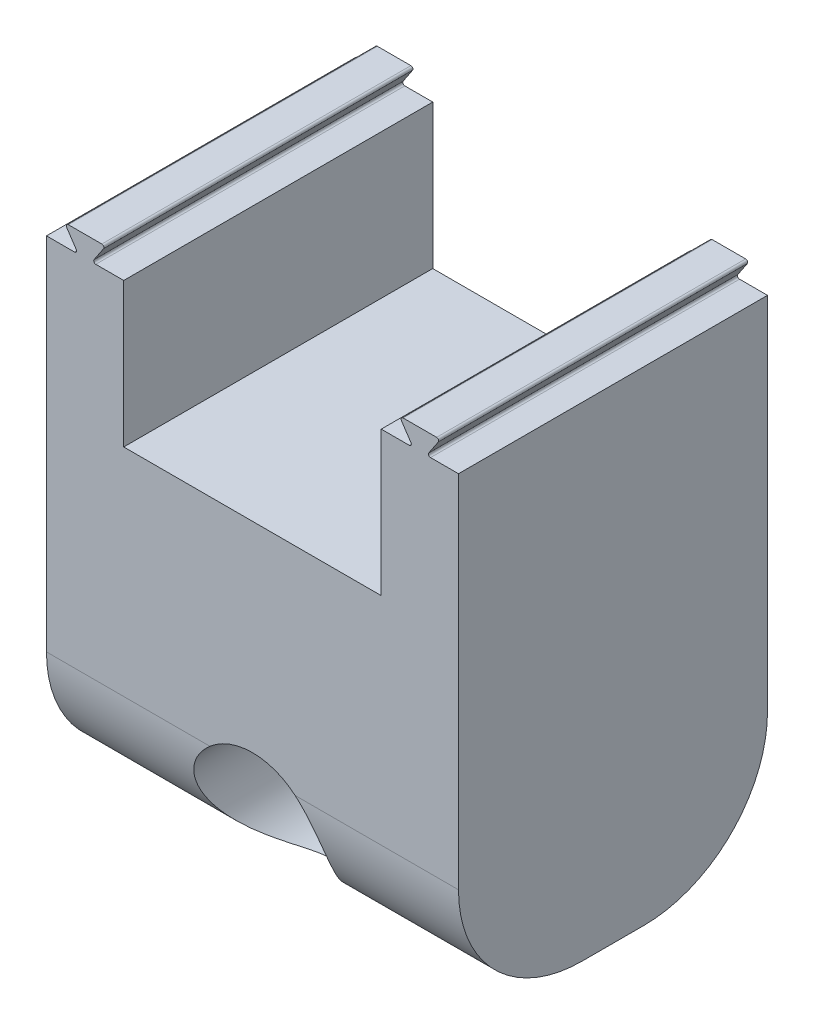
SolidWorks part; units mm, degrees
ref_plane "Front Plane" through (0, 0, 0) normal (0, 0, 1) x (1, 0, 0)
ref_plane "Top Plane" through (0, 0, 0) normal (0, 1, 0) x (1, 0, 0)
ref_plane "Right Plane" through (0, 0, 0) normal (1, 0, 0) x (0, 0, -1)
sketch "Sketch1" plane through (0, 0, 0) normal (0, 0, 1) x (1, 0, 0)
  line L2 (55, -10) -> (55, 10)
  line L3 (55, 10) -> (-55, 10)
  line L4 (-55, -10) -> (-55, 10)
  line L5 (55, -10) -> (-55, 10) construction
  line L6 (55, 10) -> (-55, -10) construction
  line L18 (40, -84.8211) -> (60, -84.8211)
  line L19 (55, -37.8397) -> (60, -37.8397)
  line L20 (55, -37.8397) -> (45, -37.8397) construction
  line L21 (43.75, -54.3304) -> (56.25, -54.3304)
  line L22 (43.75, -54.3304) -> (43.75, -68.3304)
  line L23 (43.75, -68.3304) -> (56.25, -68.3304)
  line L24 (56.25, -54.3304) -> (56.25, -68.3304)
  line L25 (50, -41.4304) -> (50, -81.2304) construction
  line L28 (40, -37.8397) -> (45, -37.8397)
  line L29 (-55, -10) -> (45, -10)
  line L30 (55, -10) -> (55, -37.8397)
  line L31 (45, -37.8397) -> (45, -10)
  line L32 (45, -37.8397) -> (55, -37.8397)
  line L33 (40, -37.8397) -> (40, -84.8211)
  line L34 (60, -37.8397) -> (60, -84.8211)
  circle A0 centre (50, -41.4304) radius 3.175
  circle A1 centre (50, -81.2304) radius 3.175
  point P0 (0, 0)
  point P9 (50, -61.3304)
  point P11 (43.75, -61.3304)
  point P18 (35, -61.3304)
  dimension "D7" = 6.35
  dimension "D1" = 20
  dimension "D2" = 110
  dimension "D3" = 12.5
  dimension "D9" = 39.8
  dimension "D10" = 14
extrude "Boss-Extrude1" add sketch "Sketch1" along normal blind 15
sketch "Sketch3" plane through (0, -54.3304, 0) normal (0, -1, 0) x (1, 0, 0)
  circle A0 centre (50, 10) radius 1.95
  dimension "D1" = 3.9
extrude "Cut-Extrude2" cut sketch "Sketch3" against normal blind 7.5
ref_plane "Plane1" through (0, 0, 7.5) normal (0, 0, 1) x (1, 0, 0)
sketch "Sketch6" plane through (0, 0, 7.5) normal (0, 0, 1) x (1, 0, 0)
  line L5 (40, -37.8397) -> (60, -37.8397) construction
  line L6 (46.25, -23.8326) -> (53.75, -23.8326)
  line L7 (50, -54.3304) -> (50, -68.3304) construction
  line L8 (43.75, -54.3304) -> (56.25, -54.3304) construction
  line L9 (43.75, -68.3304) -> (56.25, -68.3304) construction
  line L10 (50, -61.3304) -> (50, -26.1554)
  line L11 (46.25, -23.8326) -> (46.25, -37.8397)
  line L12 (46.25, -37.8397) -> (53.75, -37.8397)
  line L13 (53.75, -23.8326) -> (53.75, -37.8397)
  line L15 (53.75, -23.8326) -> (-46.25, -23.8326)
  line L16 (53.75, -23.8326) -> (53.75, -13.8326)
  line L17 (53.75, -13.8326) -> (-46.25, -13.8326)
  line L18 (-46.25, -23.8326) -> (-46.25, -13.8326)
  point P2 (50, -23.8326)
  point P13 (50, -61.3304)
  dimension "D2" = 35.175
  dimension "D1" = 7.5
  dimension "D3" = 100
  dimension "D4" = 10
extrude "Boss-Extrude2" add sketch "Sketch6" along normal mid plane 7.5
fillet "Fillet1" radius 6 2 edges at (50, -37.8397, 0) (50, -37.8397, 15)
fillet "Fillet2" radius 6 2 edges at (50, -84.8211, 0) (50, -84.8211, 15)
fillet "Fillet3" radius 5 1 edges at (3.75, -13.8326, 3.75)
fillet "Fillet4" radius 7.5 1 edges at (0, -23.8326, 3.75)
fillet "Fillet5" radius 6 2 edges at (52.0622, -38.2776, 11.25) (47.9378, -38.2776, 11.25)
fillet "Fillet6" radius 6 2 edges at (47.9378, -38.2776, 3.75) (52.0622, -38.2776, 3.75)
sketch "Sketch7" plane through (0, 0, 15) normal (0, 0, 1) x (1, 0, 0)
  line L0 (41.3576, -61.3304) -> (40, -61.3304)
  line L1 (40, -43.8397) -> (40, -78.8211) construction
  line L3 (50, -54.3304) -> (50, -68.3304) construction
  line L8 (42.6876, -60.3304) -> (41.0624, -60.3304)
  line L10 (40.9793, -60.4861) -> (41.4407, -61.1748)
  line L12 (42.7707, -60.4861) -> (42.3093, -61.1748)
  line L13 (42.3924, -61.3304) -> (43.75, -61.3304)
  line L14 (43.75, -54.3304) -> (43.75, -68.3304) construction
  line L15 (43.75, -54.3304) -> (56.25, -54.3304) construction
  line L16 (43.75, -68.3304) -> (56.25, -68.3304) construction
  line L17 (57.6076, -61.3304) -> (56.25, -61.3304)
  line L18 (57.2293, -60.4861) -> (57.6907, -61.1748)
  line L19 (57.3124, -60.3304) -> (58.9376, -60.3304)
  line L20 (59.0207, -60.4861) -> (58.5593, -61.1748)
  line L21 (58.6424, -61.3304) -> (60, -61.3304)
  line L22 (41.3576, -61.3304) -> (-57.0005, -61.3304)
  line L23 (60, -61.3304) -> (58.6424, -61.3304)
  line L24 (60, -61.3304) -> (60, -7.9559)
  line L25 (60, -7.9559) -> (-57.0005, -7.9559)
  line L26 (-57.0005, -61.3304) -> (-57.0005, -7.9559)
  line L27 (57.6076, -61.3304) -> (42.3924, -61.3304)
  arc A0 (41.3576, -61.3304) -> (41.4407, -61.1748) centre (41.3576, -61.2304) ccw
  arc A1 (41.0624, -60.3304) -> (40.9793, -60.4861) centre (41.0624, -60.4304) ccw
  arc A2 (42.3924, -61.3304) -> (42.3093, -61.1748) centre (42.3924, -61.2304) cw
  arc A3 (42.6876, -60.3304) -> (42.7707, -60.4861) centre (42.6876, -60.4304) cw
  arc A4 (57.6076, -61.3304) -> (57.6907, -61.1748) centre (57.6076, -61.2304) ccw
  arc A5 (57.3124, -60.3304) -> (57.2293, -60.4861) centre (57.3124, -60.4304) ccw
  arc A6 (58.9376, -60.3304) -> (59.0207, -60.4861) centre (58.9376, -60.4304) cw
  arc A7 (58.6424, -61.3304) -> (58.5593, -61.1748) centre (58.6424, -61.2304) cw
  line M12 (40, -43.8397) -> (40, -78.8211)
  line M14 (60, -78.8211) -> (60, -43.8397)
  line M15 (60, -43.8397) -> (52.0678, -43.8397)
  line M16 (43.75, -54.3304) -> (56.25, -54.3304)
  line M17 (56.25, -54.3304) -> (56.25, -68.3304)
  line M19 (43.75, -68.3304) -> (43.75, -54.3304)
  dimension "D4" = 0.1
  dimension "D5" = 0.1
extrude "Cut-Extrude4" cut sketch "Sketch7" against normal blind 20 contours L26 L22 L24 L25 M12 M15 | A7 L21 L0 A0 L10 A1 L8 A3 L12 A2 L13 L17 A4 L18 A5 L19 A6 L20 M14 M15 M12 M19 M16 M17
sketch "Sketch2" plane through (0, -40, 0) normal (0, -1, 0) x (1, 0, 0)
  line L0 (55, 20) -> (55, 0) construction
  circle A0 centre (40, 9.9375) radius 2.5
  dimension "D1" = 5
  dimension "D2" = 15
extrude "Cut-Extrude1" cut sketch "Sketch2" against normal blind 10
equation "\"PusherHeight\"=2"
equation "\"D1@Sketch1\"=\"PusherHeight\""
equation "\"PusherWidth\"=11"
equation "\"D2@Sketch1\"=\"PusherWidth\""
equation "\"PusherLongWidth\"=5"
equation "\"RodDiameter\"=0.5"
equation "\"HookLength\"=2.01152"
equation "\"HookHeight\"=0.999652"
equation "\"HookInnerLength\"=2"
equation "\"RodHeightDistance\"=0.4276"
equation "\"RodWidthDistance\"=0.75"
equation "\"PusherDepth\"=2"
equation "\"BuckleShaftDiameter\"=0.383646"
equation "\"BeltBuckleDistance\"=1.5"
equation "\"DowelDiameter\"=0.635"
equation "\"D7@Sketch1\"=\"DowelDiameter\""
equation "\"RodSeperationDistance\"=3.98"
equation "\"D9@Sketch1\"=\"RodSeperationDistance\""
equation "\"BuckleNutDiameter\"=0.39"
equation "\"D1@Sketch3\"=\"BuckleNutDiameter\""
equation "\"belt hole width\"=1.4"
equation "\"D10@Sketch1\"=\"belt hole width\""
equation "\"pusher height\"=3.5175"
equation "\"D2@Sketch6\"=\"pusher height\""
equation "\"pusher slot width\"=0.75"
equation "\"D1@Sketch6\"=\"pusher slot width\""
equation "\"pushing bar width\"=1"
equation "\"D4@Sketch6\"=\"pushing bar width\""
